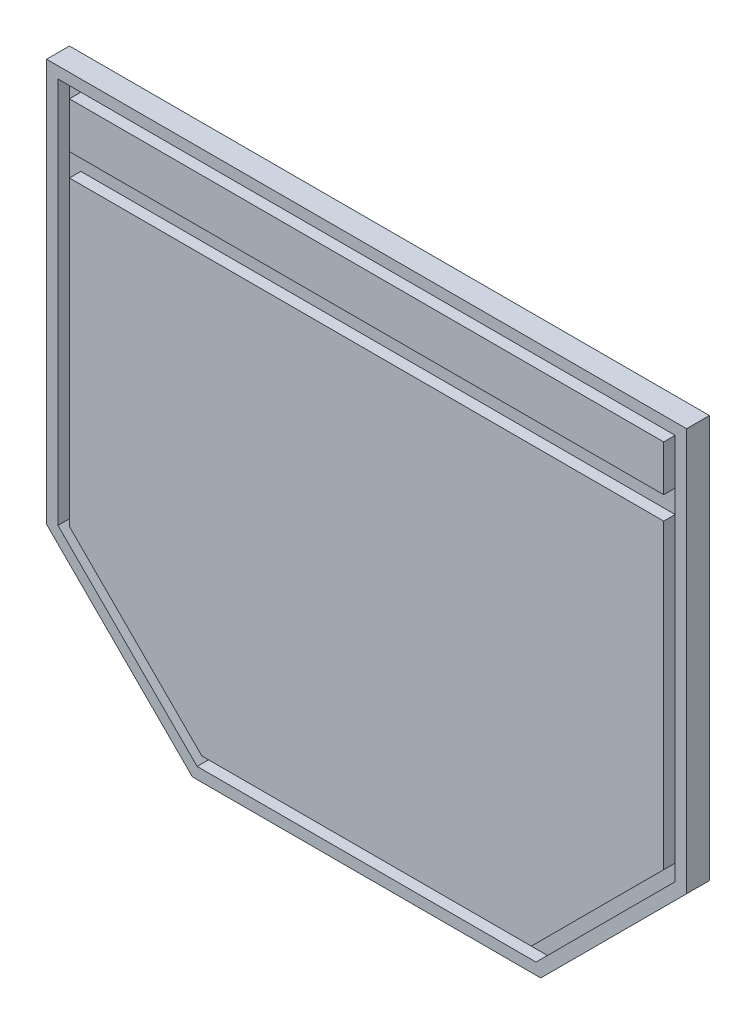
SolidWorks part; units mm, degrees
ref_plane "Front Plane" through (0, 0, 0) normal (0, 0, 1) x (1, 0, 0)
ref_plane "Top Plane" through (0, 0, 0) normal (0, 1, 0) x (1, 0, 0)
ref_plane "Right Plane" through (0, 0, 0) normal (1, 0, 0) x (0, 0, -1)
sketch "Sketch1" plane through (0, 0, 0) normal (0, 0, 1) x (1, 0, 0)
  line L0 (0, 0) -> (355.6, 0)
  line L1 (0, 0) -> (0, -223.774)
  line L2 (81.026, -304.8) -> (274.574, -304.8)
  line L3 (355.6, -223.774) -> (355.6, 0)
  line L4 (81.026, -304.8) -> (63.0655, -286.8395)
  line L5 (63.0655, -286.8395) -> (0, -223.774)
  line L6 (177.8, -304.8) -> (177.8, 0) construction
  line L7 (292.5345, -286.8395) -> (355.6, -223.774)
  line L8 (274.574, -304.8) -> (292.5345, -286.8395)
  dimension "D1" = 355.6
  dimension "D2" = 193.548
  dimension "D4" = 25.4
  dimension "D5" = 45
  dimension "D9" = 304.8
extrude "Boss-Extrude1" add sketch "Sketch1" along normal blind 12.7
sketch "Sketch2" plane through (0, 0, 12.7) normal (0, 0, 1) x (1, 0, 0)
  line L0 (6.35, -221.1437) -> (83.6563, -298.45)
  line L1 (83.6563, -298.45) -> (271.9437, -298.45)
  line L2 (271.9437, -298.45) -> (349.25, -221.1437)
  line L3 (349.25, -221.1437) -> (349.25, -6.35)
  line L4 (349.25, -6.35) -> (6.35, -6.35)
  line L5 (6.35, -6.35) -> (6.35, -221.1437)
  line L6 (0, -223.774) -> (81.026, -304.8) construction
  line L7 (81.026, -304.8) -> (274.574, -304.8) construction
  line L8 (274.574, -304.8) -> (355.6, -223.774) construction
  line L9 (355.6, -223.774) -> (355.6, 0) construction
  line L10 (0, 0) -> (0, -223.774) construction
  line L11 (355.6, 0) -> (0, 0) construction
  line L12 (12.7, -12.7) -> (12.7, -38.1)
  line L13 (12.7, -218.5135) -> (86.2865, -292.1)
  line L14 (86.2865, -292.1) -> (269.3135, -292.1)
  line L15 (269.3135, -292.1) -> (342.9, -218.5135)
  line L16 (342.9, -218.5135) -> (342.9, -50.8)
  line L17 (342.9, -12.7) -> (12.7, -12.7)
  line L18 (12.7, -38.1) -> (342.9, -38.1)
  line L19 (12.7, -50.8) -> (342.9, -50.8)
  line L20 (12.7, -50.8) -> (12.7, -218.5135)
  line L21 (12.7, -12.7) -> (12.7, -218.5135) construction
  line L22 (342.9, -38.1) -> (342.9, -12.7)
  line L23 (342.9, -218.5135) -> (342.9, -12.7) construction
  dimension "D2" = 6.35
  dimension "D3" = 6.35
  dimension "D4" = 6.35
  dimension "D5" = 6.35
  dimension "D6" = 6.35
  dimension "D7" = 6.35
  dimension "D8" = 12.7
  dimension "D9" = 25.4
  dimension "D1" = 6.35
extrude "Cut-Extrude1" cut sketch "Sketch2" against normal blind 6.35
